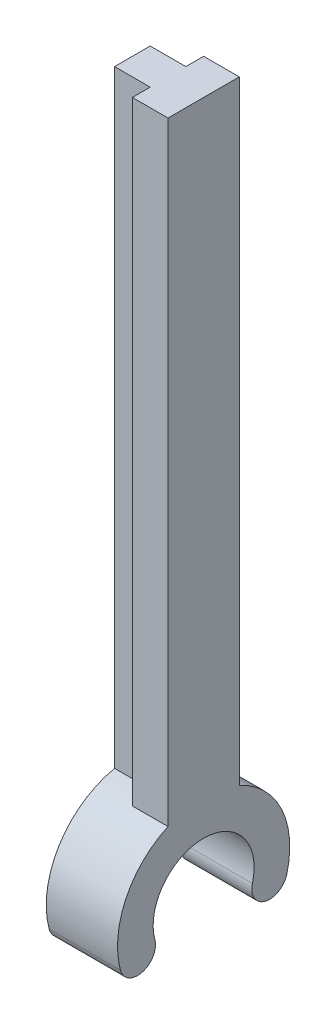
SolidWorks part; units mm, degrees
ref_plane "Front" through (0, 0, 0) normal (0, 0, 1) x (1, 0, 0)
ref_plane "Top" through (0, 0, 0) normal (0, 1, 0) x (1, 0, 0)
ref_plane "Right" through (0, 0, 0) normal (1, 0, 0) x (0, 0, -1)
sketch "Sketch1" plane through (0, 0, 0) normal (1, 0, 0) x (0, 0, -1)
  line L0 (0, 0) -> (-7.25, 0)
  line L1 (0, 0) -> (-7.003, -1.8764)
  line L2 (0, 50) -> (0, -50) construction
  line L3 (0, 0) -> (7.003, -1.8764)
  line L4 (-7.003, -1.8764) -> (-5.5541, -1.4882)
  circle A0 centre (0, 0) radius 4.25
  circle A1 centre (0, 0) radius 7.25
  arc A2 (-7.003, -1.8764) -> (-4.1052, -1.1) centre (-5.5541, -1.4882) ccw
  arc A3 (7.003, -1.8764) -> (4.1052, -1.1) centre (5.5541, -1.4882) cw
  dimension "D1" = 15
  dimension "D3" = 14.5
  dimension "D4" = 8.5
  dimension "D2" = 1.5
extrude "Boss-Extrude1" add sketch "Sketch1" against normal blind 3 and the other way blind 3 contours L3 A1 L0 A0 | A3 L3 | L0 A1 L1 A0 | L1 A2 region at (0, -0.7654, 5.8135) region at (0, 0.1713, 5.75) region at (0, -2.1031, 5.3893) region at (0, -2.1031, -5.3893)
sketch "Sketch2" plane through (0, 0, 0) normal (1, 0, 0) x (0, 0, -1)
  line L0 (0, 0) -> (0, 7.25)
  line L1 (0, 7.25) -> (0, 5.25)
  line L2 (0, 5.25) -> (-3, 5.25)
  line L4 (-3, 5.25) -> (3, 5.25)
  line L5 (-3, 5.25) -> (-3, 58.25)
  line L6 (-3, 58.25) -> (3, 58.25)
  line L7 (3, 5.25) -> (3, 58.25)
  arc A0 (7.003, -1.8764) -> (-7.003, -1.8764) centre (0, 0) ccw construction
  dimension "D1" = 2
  dimension "D2" = 3
  dimension "D3" = 6
  dimension "D4" = 53
extrude "Boss-Extrude2" add sketch "Sketch2" along normal blind 3 contours L4 L7 L6 L5 L2 region at (0, 31.75, 0)
sketch "Sketch3" plane through (0, 0, 0) normal (1, 0, 0) x (0, 0, -1)
  line L0 (0, 58.25) -> (-1.5, 58.25)
  line L1 (-3, 58.25) -> (3, 58.25) construction
  line L3 (-1.5, 58.25) -> (1.5, 58.25)
  line L4 (-1.5, 58.25) -> (-1.5, 5.25)
  line L5 (-1.5, 5.25) -> (1.5, 5.25)
  line L6 (1.5, 58.25) -> (1.5, 5.25)
  dimension "D1" = 1.5
  dimension "D2" = 53
  dimension "D3" = 3
extrude "Boss-Extrude3" add sketch "Sketch3" against normal blind 3 contours L6 L3 L0 L4 L5 region at (0, 31.75, 0)
